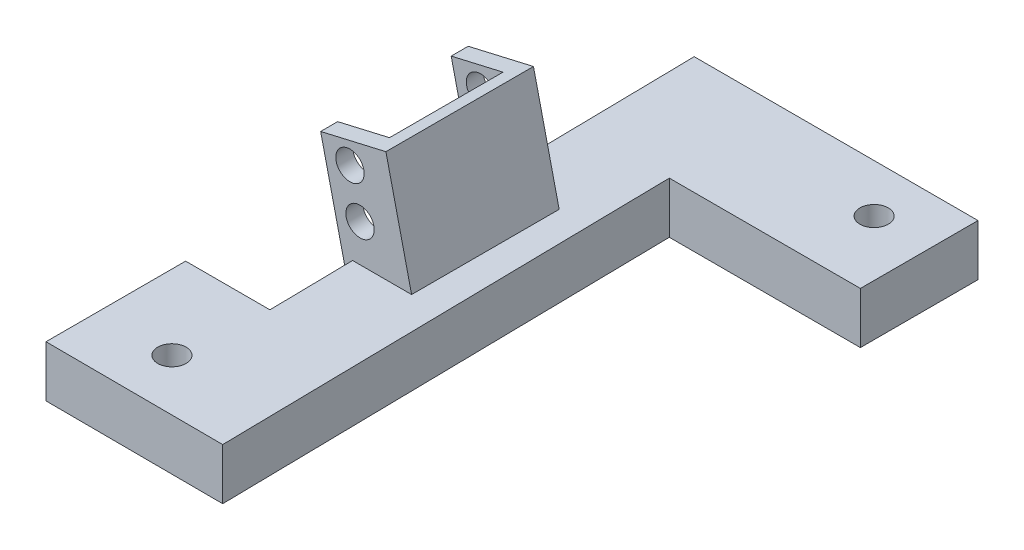
SolidWorks part; units mm, degrees
ref_plane "Front Plane" through (0, 0, 0) normal (0, 0, 1) x (1, 0, 0)
ref_plane "Top Plane" through (0, 0, 0) normal (0, 1, 0) x (1, 0, 0)
ref_plane "Right Plane" through (0, 0, 0) normal (1, 0, 0) x (0, 0, -1)
sketch "Sketch1" plane through (0, 0, 0) normal (0, 0, 1) x (1, 0, 0)
  line L0 (347.1928, 233.3099) -> (352.9388, 208.4948)
  line L1 (338.8256, 231.3724) -> (358.7891, 235.995) construction
  line L2 (352.9388, 208.4948) -> (367.5429, 211.8764)
  line L3 (367.5429, 211.8764) -> (361.7969, 236.6915)
  line L4 (361.7969, 236.6915) -> (347.1928, 233.3099)
  line L5 (338.6024, 208.4556) -> (357.7178, 212.8818) construction
  line L6 (338.6024, 208.4556) -> (357.7178, 212.8818)
  line L7 (352.2179, 211.6083) -> (357.7178, 212.8818)
  arc A0 (361.4826, 228.7505) -> (358.7891, 235.995) centre (353.7541, 230) ccw construction
  arc A1 (361.4826, 228.7505) -> (362.3955, 224.3254) centre (367.7512, 227.737) ccw construction
  arc A2 (362.9827, 217.3077) -> (362.3955, 224.3254) centre (356.0099, 220.2578) ccw construction
  arc A3 (357.7178, 212.8818) -> (362.9827, 217.3077) centre (356.0099, 220.2578) ccw construction
  arc A4 (361.4826, 228.7505) -> (358.7891, 235.995) centre (353.7541, 230) ccw
  arc A5 (361.4826, 228.7505) -> (362.3955, 224.3254) centre (367.7512, 227.737) ccw
  arc A6 (362.9827, 217.3077) -> (362.3955, 224.3254) centre (356.0099, 220.2578) ccw
  arc A7 (357.7178, 212.8818) -> (362.9827, 217.3077) centre (356.0099, 220.2578) ccw
  arc A8 (357.7178, 212.8818) -> (362.9827, 217.3077) centre (356.0099, 220.2578) ccw
  arc A9 (362.9827, 217.3077) -> (362.3955, 224.3254) centre (356.0099, 220.2578) ccw
  arc A10 (362.3955, 224.3254) -> (361.4826, 228.7505) centre (367.7512, 227.737) cw
  arc A11 (361.4826, 228.7505) -> (358.7891, 235.995) centre (353.7541, 230) ccw
extrude "Boss-Extrude1" add sketch "Sketch1" against normal blind 29.21 contours A7 L6 L0 L2 L3 L4 A4 A5 A6 region at (355.0403, 211.9324, 0)
sketch "Sketch2" plane through (0, 0, -29.21) normal (0, 0, -1) x (-1, 0, 0)
  line L0 (-358.7891, 235.995) -> (-347.1928, 233.3099)
  line L1 (-347.1928, 233.3099) -> (-352.2179, 211.6083)
  line L2 (-352.2179, 211.6083) -> (-357.7178, 212.8818)
  arc A0 (-357.7178, 212.8818) -> (-362.3955, 224.3254) centre (-356.0099, 220.2578) cw
  arc A1 (-362.3955, 224.3254) -> (-361.4826, 228.7505) centre (-367.7512, 227.737) ccw
  arc A2 (-361.4826, 228.7505) -> (-358.7891, 235.995) centre (-353.7541, 230) cw
  circle A3 centre (-353.7541, 230) radius 3.175 construction
  circle A4 centre (-356.0099, 220.2578) radius 3.175 construction
  circle A5 centre (-353.7541, 230) radius 3.175
  circle A6 centre (-356.0099, 220.2578) radius 3.175
  circle A7 centre (-356.0099, 220.2578) radius 3.175
  circle A8 centre (-353.7541, 230) radius 3.175
  arc M8 (-357.7178, 212.8818) -> (-362.3955, 224.3254) centre (-356.0099, 220.2578) cw
  arc M9 (-362.3955, 224.3254) -> (-361.4826, 228.7505) centre (-367.7512, 227.737) ccw
  arc M10 (-361.4826, 228.7505) -> (-358.7891, 235.995) centre (-353.7541, 230) cw
  line M15 (-352.2179, 211.6083) -> (-357.7178, 212.8818)
extrude "Boss-Extrude2" add sketch "Sketch2" against normal up to surface (3.81 mm away) contours L1 L0 A6 A5 M10 M9 M8 M15 region at (356.0136, 223.9731, -29.21)
sketch "Sketch3" plane through (0, 0, 0) normal (0, 0, 1) x (1, 0, 0)
  line L0 (347.1928, 233.3099) -> (352.9388, 208.4948)
  line L1 (352.9388, 208.4948) -> (367.5429, 211.8764)
  line L2 (367.5429, 211.8764) -> (361.7969, 236.6915)
  line L3 (361.7969, 236.6915) -> (347.1928, 233.3099)
  circle A0 centre (356.0099, 220.2578) radius 3.175 construction
  circle A1 centre (353.7541, 230) radius 3.175 construction
  circle A2 centre (356.0099, 220.2578) radius 3.175
  circle A3 centre (353.7541, 230) radius 3.175
  circle A4 centre (353.7541, 230) radius 3.175
  circle A5 centre (356.0099, 220.2578) radius 3.175
  arc M6 (362.3955, 224.3254) -> (357.7178, 212.8818) centre (356.0099, 220.2578) cw
  line M7 (357.7178, 212.8818) -> (352.2179, 211.6083)
  line M8 (352.2179, 211.6083) -> (352.9388, 208.4948)
  line M9 (352.9388, 208.4948) -> (367.5429, 211.8764)
  line M10 (367.5429, 211.8764) -> (361.7969, 236.6915)
  line M11 (361.7969, 236.6915) -> (358.7891, 235.995)
  arc M12 (358.7891, 235.995) -> (361.4826, 228.7505) centre (353.7541, 230) cw
  arc M13 (361.4826, 228.7505) -> (362.3955, 224.3254) centre (367.7512, 227.737) ccw
extrude "Boss-Extrude3" add sketch "Sketch3" along normal blind 3.81 contours L3 L0 A3 A2 M12 M7 M6 M13 | M13 M6 M7 M8 M9 M10 M11 M12 region at (356.0136, 223.9731, 0) region at (355.0403, 211.9324, 0)
ref_plane "Plane1" through (0, 211.8764, 0) normal (0, 1, 0) x (1, 0, 0)
sketch "Sketch5" plane through (0, 211.8764, 0) normal (0, 1, 0) x (1, 0, 0)
  line L1 (353.0649, 73.9078) -> (416.5649, 73.9078)
  line L6 (416.5649, 73.9078) -> (416.5649, 47.5898)
  line L7 (416.5649, 47.5898) -> (373.8144, 47.5898)
  line L8 (373.8144, 47.5898) -> (375.4776, -54.0102)
  line L9 (335.7799, -53.8514) -> (335.7799, -22.6122)
  line L10 (335.7799, -22.6122) -> (354.645, -22.6122)
  line L11 (354.645, -22.6122) -> (353.0649, 73.9078)
  line L12 (335.7799, -53.8514) -> (375.4776, -54.0102)
  circle A0 centre (404.0733, 63.1493) radius 3.175
  circle A1 centre (352.4976, -42.3935) radius 3.175
  circle A2 centre (352.4976, -42.3935) radius 3.175 construction
  dimension "D1" = 6.35
  dimension "D6" = 6.35
  dimension "D2" = 96.52
  dimension "D3" = 101.6
  dimension "D4" = 63.5
  dimension "D5" = 31.2392
  dimension "D7" = 11.5246
  dimension "D8" = 16.7177
  dimension "D9" = 7.112
  dimension "D10" = 20.3159
  dimension "D11" = 270
extrude "Boss-Extrude4" add sketch "Sketch5" against normal up to surface (11.4704 mm away)
